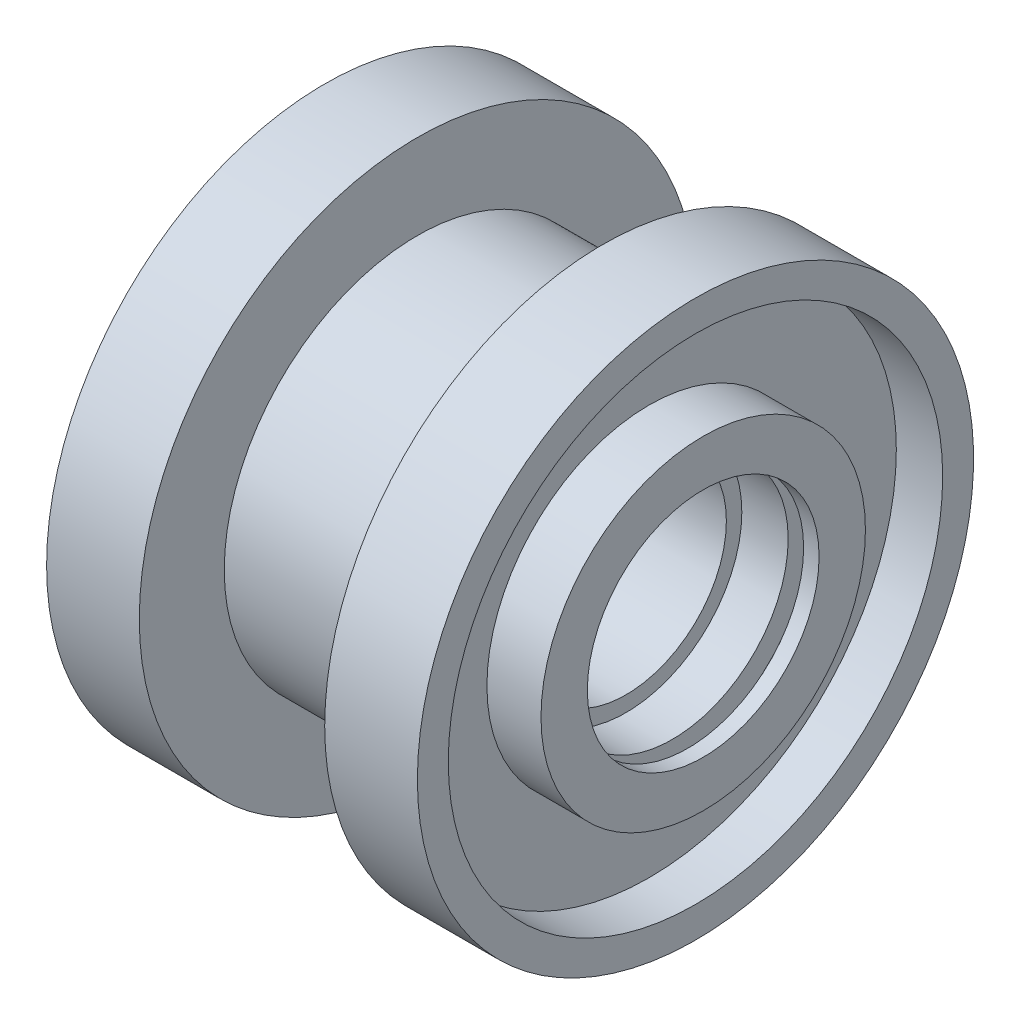
SolidWorks part; units mm, degrees
material "PS HI"
ref_plane "Płaszczyzna przednia" through (0, 0, 0) normal (0, 0, 1) x (1, 0, 0)
ref_plane "Płaszczyzna górna" through (0, 0, 0) normal (0, 1, 0) x (1, 0, 0)
ref_plane "Płaszczyzna prawa" through (0, 0, 0) normal (1, 0, 0) x (0, 0, -1)
sketch "Szkic1" plane through (0, 0, 0) normal (0, 0, 1) x (1, 0, 0)
  line L0 (-12.5, 0) -> (12.5, 0) construction
  line L1 (0, -18) -> (0, 18) construction
  line L2 (-6, 12.5) -> (6, 12.5)
  line L3 (6, 12.5) -> (6, 18)
  line L4 (6, 18) -> (12, 18)
  line L5 (12, 18) -> (12, 16)
  line L6 (12, 16) -> (9, 16)
  line L7 (9, 16) -> (9, 10.5)
  line L10 (-12, 16) -> (-9, 16)
  line L11 (-12, 18) -> (-12, 16)
  line L12 (-6, 18) -> (-12, 18)
  line L13 (-6, 12.5) -> (-6, 18)
  line L15 (12.5, 7.5) -> (12.5, 10.5)
  line L16 (12.5, 10.5) -> (9, 10.5)
  line L18 (-9, 16) -> (-9, 10.5)
  line L20 (-12.5, 7.5) -> (-12.5, 10.5)
  line L21 (-12.5, 10.5) -> (-9, 10.5)
  line L22 (12.5, 7.5) -> (11.5, 7.5)
  line L23 (7.5, 7.5) -> (7.5, 6.5)
  line L24 (7.5, 6.5) -> (-7.5, 6.5)
  line L25 (-7.5, 7.5) -> (-10.5, 7.5)
  line L26 (-7.5, 7.5) -> (-7.5, 6.5)
  line L27 (11.5, 7.5) -> (11.5, 8.9)
  line L28 (11.5, 8.9) -> (10.5, 8.9)
  line L29 (10.5, 8.9) -> (10.5, 7.5)
  line L30 (10.5, 7.5) -> (7.5, 7.5)
  line L31 (-11.5, 7.5) -> (-11.5, 8.9)
  line L32 (-10.5, 8.9) -> (-10.5, 7.5)
  line L33 (-11.5, 8.9) -> (-10.5, 8.9)
  line L34 (-11.5, 7.5) -> (-12.5, 7.5)
  point P1 (12, 17)
  point P7 (0, 0)
  point P14 (0, 7.5)
  point P15 (7.5, 7.5)
  point P21 (0, 12.5)
  point P23 (12.5, 9)
  point P32 (0, 6.5)
  dimension "D2" = 25
  dimension "D3" = 32
  dimension "D4" = 36
  dimension "D5" = 3
  dimension "D6" = 6
  dimension "D7" = 12
  dimension "D8" = 21
  dimension "D9" = 3.5
  dimension "D10" = 25
  dimension "D11" = 5
  dimension "D12" = 13
  dimension "D14" = 1
  dimension "D15" = 3
  dimension "D16" = 15
  dimension "D17" = 17.8
revolve "Obrót1" add sketch "Szkic1" angle 360 about L0
sketch "Szkic2" plane through (-12, 0, 0) normal (-1, 0, 0) x (0, 0, 1)
  line L0 (0, 18) -> (0, 16) construction
  circle A0 centre (0, 17) radius 0.5
  dimension "D1" = 0.5
extrude "Wytnij-wyciągnięcie1" cut sketch "Szkic2" against normal blind 1
